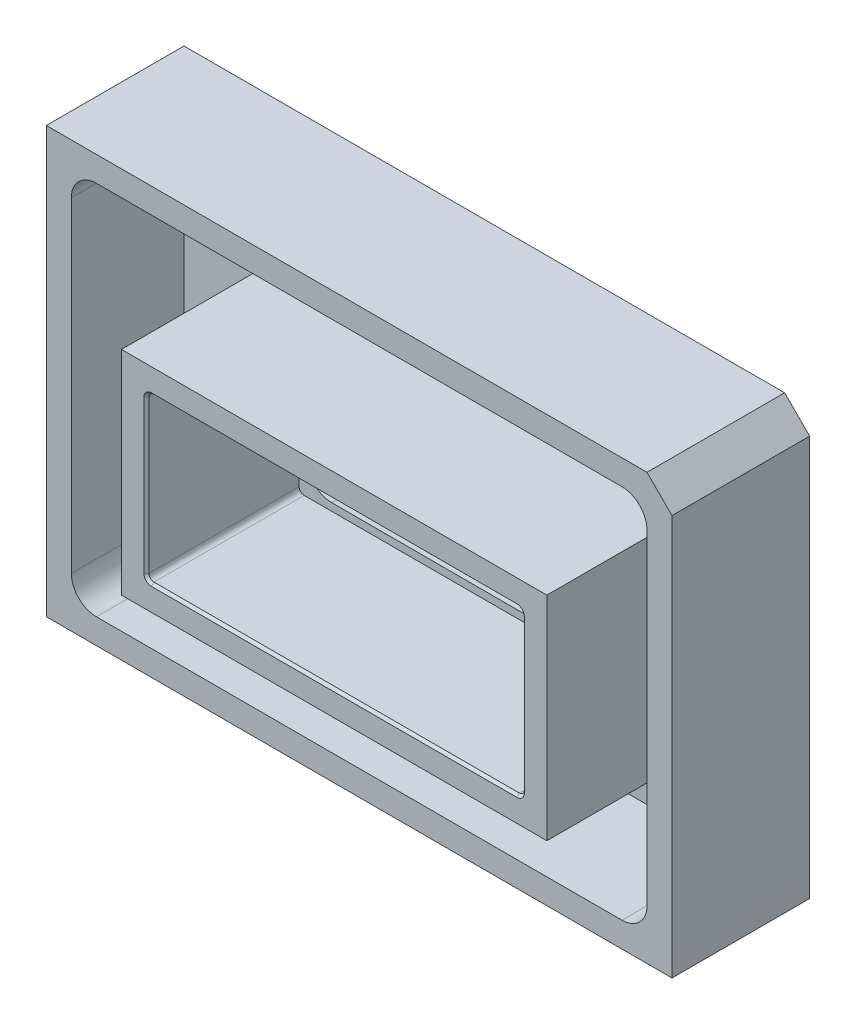
SolidWorks part; units mm, degrees
material "AISI Type 316L stainless steel"
ref_plane "Front Plane" through (0, 0, 0) normal (0, 0, 1) x (1, 0, 0)
ref_plane "Top Plane" through (0, 0, 0) normal (0, 1, 0) x (1, 0, 0)
ref_plane "Right Plane" through (0, 0, 0) normal (1, 0, 0) x (0, 0, -1)
sketch "Sketch1" plane through (0, 0, 0) normal (0, 0, 1) x (1, 0, 0)
  line L1 (75, -32.5) -> (-75, -32.5)
  line L2 (75, -32.5) -> (75, 32.5)
  line L3 (75, 32.5) -> (-75, 32.5)
  line L4 (-75, -32.5) -> (-75, 32.5)
  line L5 (75, -32.5) -> (-75, 32.5) construction
  line L6 (75, 32.5) -> (-75, -32.5) construction
  line L7 (125, -75) -> (-125, -75)
  line L8 (125, -75) -> (125, 95)
  line L9 (125, 95) -> (-125, 95)
  line L10 (-125, -75) -> (-125, 95)
  line L11 (125, -75) -> (-125, 95) construction
  line L12 (125, 95) -> (-125, -75) construction
  point P0 (0, 0)
  point P10 (0, 10)
  dimension "D1" = 65
  dimension "D2" = 150
  dimension "D3" = 250
  dimension "D4" = 170
  dimension "D5" = 10
extrude "Boss-Extrude3" add sketch "Sketch1" along normal blind 65 contours L9 L10 L7 L8
extrude "Cut-Extrude1" cut sketch "Sketch1<3>" along normal through all from offset 4 contours L4 L1 L2 L3 region at (0, 0, 0)
sketch "Sketch1<3>" plane through (0, 0, 0) normal (0, 0, 1) x (1, 0, 0) same geometry as "Sketch1"
sketch "Sketch6" plane through (0, 0, 65) normal (0, 0, 1) x (1, 0, 0)
  line L0 (-75, -32.5) -> (-75, 32.5) construction
  line L1 (85, -42.5) -> (-85, -42.5)
  line L2 (85, -42.5) -> (85, 42.5)
  line L3 (85, 42.5) -> (-85, 42.5)
  line L4 (-85, -42.5) -> (-85, 42.5)
  line L5 (85, -42.5) -> (-85, 42.5) construction
  line L6 (85, 42.5) -> (-85, -42.5) construction
  line L7 (75, 32.5) -> (-75, 32.5) construction
  line L8 (-125, -75) -> (-125, 95) construction
  line L9 (115, -65) -> (-115, -65)
  line L10 (115, -65) -> (115, 85)
  line L11 (115, 85) -> (-115, 85)
  line L12 (-115, -65) -> (-115, 85)
  line L13 (115, -65) -> (-115, 85) construction
  line L14 (115, 85) -> (-115, -65) construction
  line L15 (125, 95) -> (-125, 95) construction
  line L16 (125, -75) -> (-125, -75) construction
  line L17 (125, -75) -> (125, 95) construction
  point P0 (0, 0)
  point P10 (0, 0)
  dimension "D1" = 10
  dimension "D2" = 10
  dimension "D3" = 10
  dimension "D4" = 10
  dimension "D5" = 10
  dimension "D6" = 10
extrude "Cut-Extrude2" cut sketch "Sketch6" against normal offset from surface (55 mm away) 10 up to face at (0, 10, 0)
sketch "Sketch7" plane through (0, 0, 4) normal (0, 0, 1) x (1, 0, 0)
  line L0 (75, 32.5) -> (-75, 32.5) construction
  line L1 (72, -29.5) -> (-72, -29.5)
  line L2 (72, -29.5) -> (72, 29.5)
  line L3 (72, 29.5) -> (-72, 29.5)
  line L4 (-72, -29.5) -> (-72, 29.5)
  line L5 (72, -29.5) -> (-72, 29.5) construction
  line L6 (72, 29.5) -> (-72, -29.5) construction
  line L7 (-75, -32.5) -> (-75, 32.5) construction
  point P0 (0, 0)
  dimension "D1" = 3
  dimension "D2" = 3
extrude "Cut-Extrude3" cut sketch "Sketch7" against normal through all
sketch "Sketch8" plane through (0, -75, 0) normal (0, -1, 0) x (-1, 0, 0)
  line L0 (0, 35.75) -> (0, -35.75) construction
  line L1 (-125, 0) -> (125, 0) construction
  point P0 (60, -5)
  point P1 (0, -5)
  point P4 (-60, -5)
  dimension "D1" = 5
  dimension "D2" = 60
hole_wizard "Tap Drill for M3 Tap1" positions "Sketch10" profile "Sketch12" hole size "M3" standard "GB"
sketch "Sketch10" plane through (0, -75, 0) normal (0, -1, 0) x (-1, 0, 0)
  point P0 (-60, -5)
  point P3 (0, -5)
  point P6 (60, -5)
sketch "Sketch12" plane through (60, -75, 5) normal (1, 0, 0) x (0, 0, -1)
  line L0 (0, 0) -> (0, 5.7511)
  line L1 (0, 5.7511) -> (1.25, 5)
  line L2 (1.25, 5) -> (1.25, 0)
  line L5 (1.25, 0) -> (0, 0)
  line L10 (0, 5.7511) -> (-1.25, 5) construction
  line L11 (0, -6.35) -> (0, 107.95) construction
  dimension "Hole Dia." = 2.5
  dimension "Hole Depth" = 5
  dimension "Drill Angle" = 118
sketch "Sketch16" plane through (-125, 0, 0) normal (-1, 0, 0) x (0, 0, 1)
  line L0 (35.75, 0) -> (-35.75, 0) construction
  line L1 (0, -75) -> (0, 95) construction
  point P0 (5, 0)
  point P1 (5, 60)
  point P4 (5, -60)
  dimension "D1" = 5
  dimension "D2" = 60
hole_wizard "Tap Drill for M3 Tap3" positions "Sketch17" profile "Sketch18" hole size "M3" standard "GB"
sketch "Sketch17" plane through (-125, 0, 0) normal (-1, 0, 0) x (0, 0, 1)
  point P0 (5, 60)
  point P3 (5, 0)
  point P6 (5, -60)
sketch "Sketch18" plane through (-125, 60, 5) normal (0, 1, 0) x (0, 0, 1)
  line L0 (0, 0) -> (0, 5.7511)
  line L1 (0, 5.7511) -> (1.25, 5)
  line L2 (1.25, 5) -> (1.25, 0)
  line L5 (1.25, 0) -> (0, 0)
  line L10 (0, 5.7511) -> (-1.25, 5) construction
  line L11 (0, -6.35) -> (0, 107.95) construction
  dimension "Hole Dia." = 2.5
  dimension "Hole Depth" = 5
  dimension "Drill Angle" = 118
fillet "Fillet3" radius 10 8 edges at (115, 85, 37.5) (115, -65, 37.5) (-115, -65, 37.5) (-115, 85, 37.5) (72, 29.5, 2) (72, -29.5, 2) (-72, -29.5, 2) (-72, 29.5, 2)
sketch "Sketch19" plane through (0, 0, 65) normal (0, 0, 1) x (1, 0, 0)
  line L4 (-105, -65) -> (105, -65)
  line L5 (-115, 75) -> (-115, -55)
  line L6 (105, 85) -> (-105, 85)
  line L7 (115, -55) -> (115, 75)
  line L9 (-115, 75) -> (-115, -55)
  line L10 (105, 85) -> (-105, 85)
  line L11 (115, -55) -> (115, 75)
  line L12 (125, -75) -> (125, 95)
  line L13 (125, 95) -> (-125, 95)
  line L14 (-125, 95) -> (-125, -75)
  line L15 (-125, -75) -> (125, -75)
  line L16 (125, -75) -> (125, 95)
  line L17 (125, 95) -> (-125, 95)
  line L18 (-125, 95) -> (-125, -75)
  line L19 (-125, -75) -> (125, -75)
  line L20 (-105, -65) -> (105, -65)
  arc A5 (-105, 85) -> (-115, 75) centre (-105, 75) ccw
  arc A6 (115, 75) -> (105, 85) centre (105, 75) ccw
  arc A9 (-105, 85) -> (-115, 75) centre (-105, 75) ccw
  arc A10 (115, 75) -> (105, 85) centre (105, 75) ccw
  arc A14 (-115, -55) -> (-105, -65) centre (-105, -55) ccw
  arc A15 (-115, -55) -> (-105, -65) centre (-105, -55) ccw
  arc A16 (105, -65) -> (115, -55) centre (105, -55) ccw
  arc A17 (105, -65) -> (115, -55) centre (105, -55) ccw
  dimension "D1" = 0
  dimension "D2" = 0
extrude "Cut-Extrude4" cut sketch "Sketch19" against normal blind 10
fillet "Fillet2" radius 2 4 edges at (-75, -32.5, 34.5) (75, -32.5, 34.5) (75, 32.5, 34.5) (-75, 32.5, 34.5)
chamfer "Chamfer1" distance 1 angle 45 8 edges at (0, -32.5, 65) (74.4142, -31.9142, 65) (-74.4142, -31.9142, 65) (75, 0, 65) (-75, 0, 65) (74.4142, 31.9142, 65) (-74.4142, 31.9142, 65) (0, 32.5, 65)
chamfer "Chamfer2" distance 10 angle 45 1 edges at (125, 95, 27.5)
